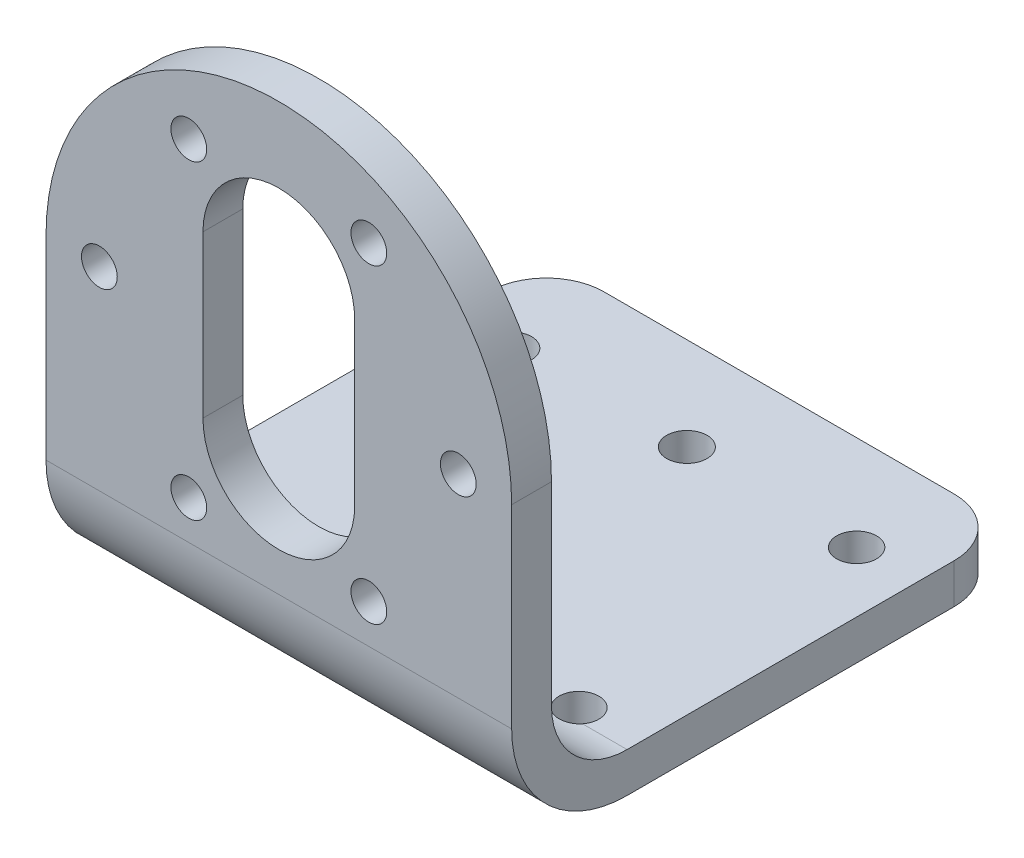
SolidWorks part; units mm, degrees
ref_plane "Front Plane" through (0, 0, 0) normal (0, 0, 1) x (1, 0, 0)
ref_plane "Top Plane" through (0, 0, 0) normal (0, 1, 0) x (1, 0, 0)
ref_plane "Right Plane" through (0, 0, 0) normal (1, 0, 0) x (0, 0, -1)
sketch "Sketch1" plane through (0, 0, 0) normal (0, 1, 0) x (1, 0, 0)
  line L1 (-47.1412, -7.433) -> (-6.7912, -7.433)
  line L2 (-47.1412, -7.433) -> (-47.1412, -50.783)
  line L3 (-47.1412, -50.783) -> (-6.7912, -50.783)
  line L4 (-6.7912, -7.433) -> (-6.7912, -50.783)
extrude "Boss-Extrude1" add sketch "Sketch1" along normal blind 47
sketch "Sketch3" plane through (0, 0, 50.783) normal (0, 0, 1) x (1, 0, 0)
  line L6 (-47.1412, 26.825) -> (-47.1412, 47)
  line L7 (-47.1412, 47) -> (-6.7912, 47)
  line L8 (-6.7912, 26.825) -> (-6.7912, 47)
  arc A1 (-6.7912, 26.825) -> (-47.1412, 26.825) centre (-26.9662, 26.825) ccw
  line M2 (-6.7912, 0) -> (-6.7912, 47)
  line M3 (-6.7912, 47) -> (-47.1412, 47)
  line M4 (-47.1412, 47) -> (-47.1412, 0)
extrude "Cut-Extrude2" cut sketch "Sketch3" against normal blind 102 contours A1 L7 M4 | A1 M2 M3 region at (-11.2977, 42.4936, 50.783) region at (-42.6348, 42.4936, 50.783)
fillet "Fillet1" radius 10 1 edges at (-26.9662, 0, 50.783)
sketch "Sketch5" plane through (-47.1412, 0, 0) normal (-1, 0, 0) x (0, 0, 1)
  line L0 (7.433, 0) -> (-6.6658, 0)
  line L1 (-6.6658, 0) -> (-6.6658, 3.45)
  line L2 (50.783, 47) -> (50.783, 59.7784)
  line L3 (50.783, 59.7784) -> (47.333, 59.7784)
  line L5 (-6.6658, 3.45) -> (36.5956, 3.45)
  line L6 (-6.6658, 3.45) -> (-6.6658, 59.7784)
  line L7 (-6.6658, 59.7784) -> (47.333, 59.7784)
  line L8 (47.333, 17.5785) -> (47.333, 59.7784)
  line L9 (36.5956, 3.45) -> (40.783, 3.45)
  line L12 (47.333, 10) -> (47.333, 17.5785)
  arc A1 (40.783, 3.45) -> (47.333, 10) centre (40.783, 10) ccw
  line M2 (50.783, 26.825) -> (7.433, 26.825)
  line M3 (7.433, 26.825) -> (7.433, 0)
extrude "Cut-Extrude3" cut sketch "Sketch5" against normal blind 102 contours L8 L7 L6 L5 M2 M3 | L5 L8 M2 M3 region at (-47.1412, 15.2394, 27.1987) region at (-47.1412, 38.9007, 17.2162)
fillet "Fillet2" radius 5 2 edges at (-6.7912, 1.725, 7.433) (-47.1412, 1.725, 7.433)
sketch "Sketch6" plane through (0, 3.45, 0) normal (0, 1, 0) x (1, 0, 0)
  line L0 (-27.9141, -7.433) -> (-27.9141, -13.933)
  line L1 (-42.1412, -7.433) -> (-11.7912, -7.433) construction
  line L2 (-47.1412, -24.2783) -> (-43.6412, -24.2783)
  line L3 (-47.1412, -12.433) -> (-47.1412, -40.783) construction
  line L4 (-6.7912, -25.5422) -> (-10.2912, -25.5422)
  line L5 (-6.7912, -12.433) -> (-6.7912, -40.783) construction
  line L6 (-43.6412, -24.2783) -> (-43.6412, -13.933)
  line L7 (-43.6412, -13.933) -> (-10.2912, -13.933)
  line L8 (-10.2912, -13.933) -> (-10.2912, -45.493)
  line L9 (-10.2912, -45.493) -> (-43.6412, -45.493)
  line L10 (-43.6412, -45.493) -> (-43.6412, -24.2783)
  line L11 (-41.9112, -17.393) -> (-41.9112, -37.993)
  line L12 (-12.0212, -17.393) -> (-12.0212, -37.993)
  circle A0 centre (-41.9112, -15.663) radius 1.73
  circle A1 centre (-12.0212, -15.663) radius 1.73
  circle A2 centre (-41.9112, -39.723) radius 1.73
  circle A3 centre (-12.0212, -39.723) radius 1.73
  line M12 (-47.1412, -40.783) -> (-6.7912, -40.783)
extrude "Cut-Extrude4" cut sketch "Sketch6" against normal blind 102 and the other way blind 102 contours A3 M12 | A3 M12 | A2 M12 | A2 M12 | A1 | A0 region at (-41.9112, 3.45, 15.663) region at (-41.9112, 3.45, 39.5133) region at (-41.9112, 3.45, 41.056) region at (-12.0212, 3.45, 15.663) region at (-12.0212, 3.45, 41.056) region at (-12.0212, 3.45, 39.5133)
sketch "Sketch7" plane through (0, 0, 50.783) normal (0, 0, 1) x (1, 0, 0)
  line L0 (-47.1412, 21.9829) -> (-33.5412, 21.9829)
  line L2 (-33.5412, 33.925) -> (-33.5412, 19.945)
  line L4 (-20.3912, 33.925) -> (-20.3912, 19.945)
  line L5 (-47.1412, 26.825) -> (-47.1412, 10) construction
  line L6 (-20.3912, 20.4169) -> (-6.7912, 20.4169)
  line L7 (-6.7912, 26.825) -> (-6.7912, 10) construction
  line L8 (-26.9662, 47) -> (-26.9662, 40.5)
  arc A0 (-6.7912, 26.825) -> (-47.1412, 26.825) centre (-26.9662, 26.825) ccw construction
  arc A1 (-20.3912, 33.925) -> (-33.5412, 33.925) centre (-26.9662, 33.925) ccw
  arc A2 (-33.5412, 19.945) -> (-20.3912, 19.945) centre (-26.9662, 19.945) ccw
extrude "Cut-Extrude5" cut sketch "Sketch7" against normal blind 102 contours L2 A2 L4 A1 region at (-26.9662, 26.935, 50.783)
sketch "Sketch8" plane through (0, 0, 50.783) normal (0, 0, 1) x (1, 0, 0)
  line L4 (-40.9662, 26.825) -> (-44.0662, 26.825)
  line L5 (-12.9662, 26.825) -> (-9.8662, 26.825)
  arc A0 (-33.8891, 38.9936) -> (-20.0433, 38.9936) centre (-26.9662, 26.825) ccw
  arc A1 (-35.5437, 41.6181) -> (-18.3887, 41.6181) centre (-26.9662, 26.825) ccw
  arc A2 (-20.0433, 14.6564) -> (-20.0519, 14.6448) centre (-26.9662, 19.725) cw
  arc A3 (-33.8806, 39.0052) -> (-33.8891, 38.9936) centre (-26.9662, 33.925) ccw
  circle A4 centre (-34.7662, 40.2772) radius 1.55
  circle A5 centre (-19.1662, 40.2772) radius 1.55
  circle A6 centre (-19.1662, 13.3728) radius 1.55
  arc A7 (-20.0433, 38.9936) -> (-20.0519, 39.0052) centre (-26.9662, 33.925) ccw
  circle A8 centre (-34.7662, 13.3728) radius 1.55
  arc A9 (-33.8806, 14.6448) -> (-33.8891, 14.6564) centre (-26.9662, 19.725) cw
  circle A10 centre (-42.5162, 26.825) radius 1.55
  circle A11 centre (-11.4162, 26.825) radius 1.55
extrude "Cut-Extrude6" cut sketch "Sketch8" against normal blind 102 contours A8 | A6 | L5 A11 | L5 A11 | L4 A10 | L4 A10 | A4 | A5 A4 region at (-42.5162, 26.1672, 50.783) region at (-42.5162, 27.4828, 50.783) region at (-34.7662, 40.2772, 50.783) region at (-34.7662, 13.3728, 50.783) region at (-19.1662, 13.3728, 50.783) region at (-11.4162, 26.1672, 50.783) region at (-11.4162, 27.4828, 50.783) region at (-19.1662, 40.2772, 50.783)
sketch "Sketch9" plane through (0, 0, 0) normal (0, -1, 0) x (1, 0, 0)
  line L2 (-11.7912, 7.433) -> (-42.1412, 7.433) construction
  circle A0 centre (-26.9112, 15.483) radius 1.75
  arc A1 (-43.2784, 40.783) -> (-40.544, 40.783) centre (-41.9112, 39.723) ccw construction
  point P5 (0, 0)
  point P8 (-63.1419, 45.5763)
  dimension "D1" = 3.5
  dimension "D2" = 15
  dimension "D3" = 8.05
extrude "Cut-Extrude7" cut sketch "Sketch9" against normal blind 10
